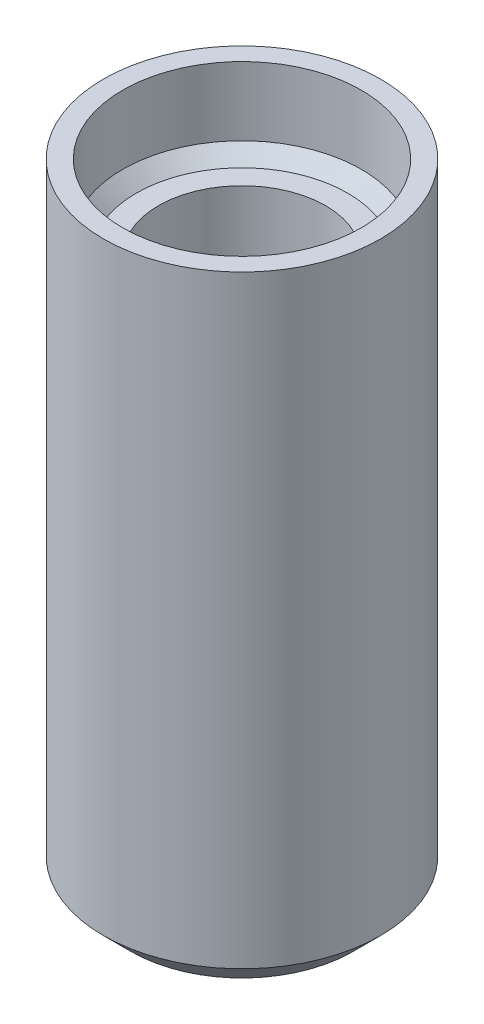
SolidWorks part; units mm, degrees
ref_plane "Front Plane" through (0, 0, 0) normal (0, 0, 1) x (1, 0, 0)
ref_plane "Top Plane" through (0, 0, 0) normal (0, 1, 0) x (1, 0, 0)
ref_plane "Right Plane" through (0, 0, 0) normal (1, 0, 0) x (0, 0, -1)
sketch "Sketch1" plane through (0, 0, 0) normal (0, 1, 0) x (1, 0, 0)
  line L0 (-2.5652, -1.65) -> (2.5652, -1.65)
  circle A0 centre (0, 0) radius 3.05
  circle A1 centre (0, 0) radius 5.05
  dimension "D1" = 6.1
  dimension "D3" = 1.65
  dimension "D2" = 2
extrude "Boss-Extrude1" add sketch "Sketch1" along normal blind 20 contours A1 A0 | L0 A0 region at (0, 0, 2.2227) region at (-4.9072, 0, 0)
sketch "Sketch2" plane through (0, 0, 0) normal (0, -1, 0) x (1, 0, 0)
  circle A1 centre (0, 0) radius 5.05
  circle A2 centre (0, 0) radius 5.05
  dimension "D1" = 0
extrude "Boss-Extrude2" add sketch "Sketch2" against normal blind 2
sketch "Sketch4" plane through (0, 20, 0) normal (0, 1, 0) x (1, 0, 0)
  circle A0 centre (0, 0) radius 4.35
  circle A1 centre (0, 0) radius 5.05
  circle A2 centre (0, 0) radius 5.05
  dimension "D1" = 0
  dimension "D2" = 0.7
extrude "Boss-Extrude3" add sketch "Sketch4" along normal blind 3
chamfer "Chamfer1" distance 1 angle 45 1 edges at (0, 0, 5.05)
chamfer "Chamfer2" distance 0.5 angle 45 1 edges at (0, 20, 4.35)
sketch "Sketch5" plane through (0, 0, 0) normal (0, -1, 0) x (1, 0, 0)
  line L0 (-1.326, 0) -> (1.326, 0) construction
  line L1 (-3.5217, -2) -> (3.5217, -2) construction
  circle A0 centre (0, 0) radius 4.05 construction
  text T0 "<b>2</b>" font "Calibri" height in points 16
  dimension "D1" = 2
extrude "Cut-Extrude1" cut sketch "Sketch5" against normal blind 0.4
extrude "Boss-Extrude4" add sketch "Sketch5<2>" against normal blind 0.4 separate body
sketch "Sketch5<2>" plane through (0, 0, 0) normal (0, -1, 0) x (1, 0, 0) same geometry as "Sketch5"
equation "\"ID\"= 6.3"
equation "\"notch\"= 6.3 / 2 - 1.5"
equation "\"D3@Sketch1\"=\"notch\""
